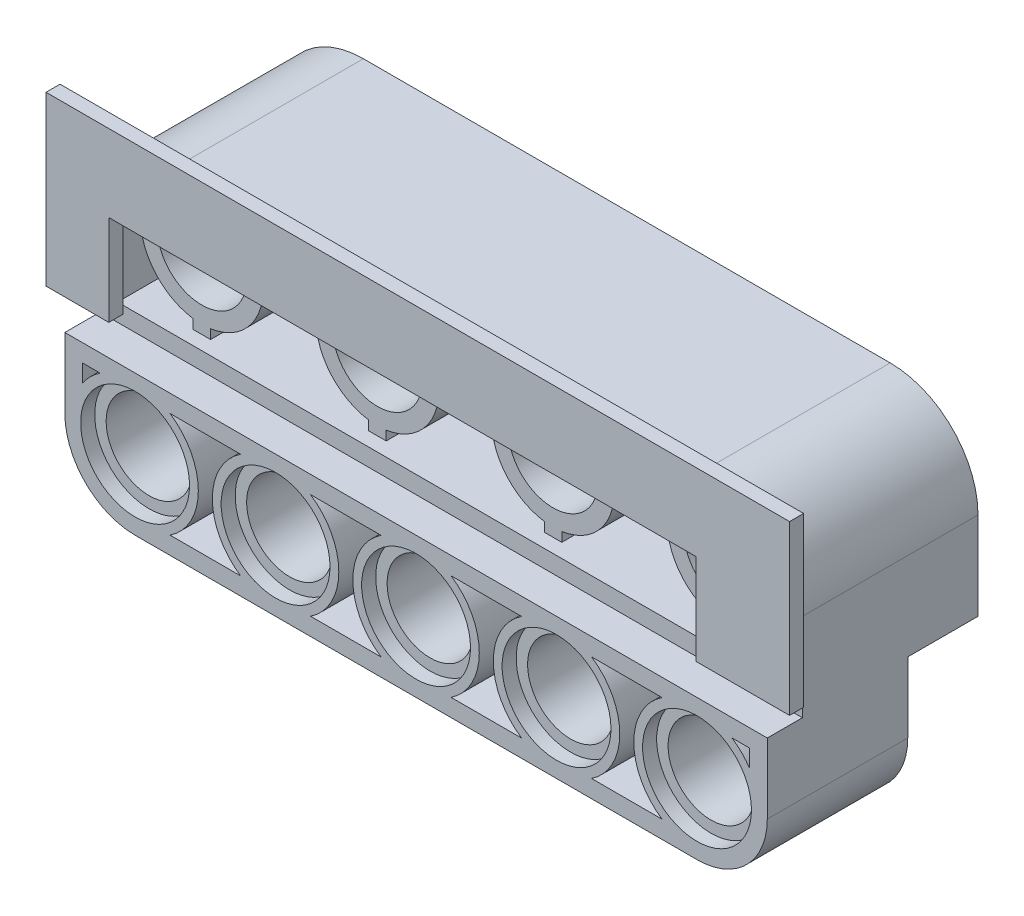
SolidWorks part; units mm, degrees
ref_plane "Front Plane" through (0, 0, 0) normal (0, 0, 1) x (1, 0, 0)
ref_plane "Top Plane" through (0, 0, 0) normal (0, 1, 0) x (1, 0, 0)
ref_plane "Right Plane" through (0, 0, 0) normal (1, 0, 0) x (0, 0, -1)
sketch "Sketch1" plane through (0, 0, 0) normal (1, 0, 0) x (0, 0, -1)
  line L0 (-5, -5) -> (-5, -13)
  line L1 (5, 5) -> (-5, 5)
  line L2 (5, 5) -> (5, -5)
  line L3 (5, -5) -> (-5, -5)
  line L4 (-5, 5) -> (-5, -5)
  line L5 (5, 5) -> (-5, -5) construction
  line L6 (5, -5) -> (-5, 5) construction
  line L7 (-5, -13) -> (3, -13)
  line L8 (3, -13) -> (3, -5)
  point P0 (0, 0)
  dimension "D1" = 10
  dimension "D2" = 10
  dimension "D3" = 8
  dimension "D4" = 8
extrude "Boss-Extrude1" add sketch "Sketch1" along normal blind 40 contours L1 L4 L3 L2 | L7 L8 L3 L0 region at (0, -9, 1) region at (0, 0, 0)
sketch "Sketch2" plane through (0, 0, -5) normal (0, 0, -1) x (-1, 0, 0)
  line L0 (-40, 0) -> (0, 0) construction
  line L1 (-40, 5) -> (-40, -5) construction
  line L2 (0, 5) -> (0, -5) construction
  line L3 (-35, 0) -> (-35, -7.7251) construction
  line L4 (-35, -7.7251) -> (-25, -7.7251) construction
  line L5 (-25, -7.7251) -> (-25, 0) construction
  line L6 (-25, 0) -> (-25, 7.4414) construction
  line L7 (-25, 7.4414) -> (-15, 7.4414) construction
  line L8 (-15, 7.4414) -> (-15, 0) construction
  line L9 (-15, 0) -> (-15, -7.7251) construction
  line L10 (-15, -7.7251) -> (-5, -7.7251) construction
  line L11 (-5, -7.7251) -> (-5, 0) construction
  circle A0 centre (-35, 0) radius 2.5
  circle A1 centre (-25, 0) radius 2.5
  circle A2 centre (-15, 0) radius 2.5
  circle A3 centre (-5, 0) radius 2.5
  dimension "D2" = 5
  dimension "D1" = 5
  dimension "D3" = 10
extrude "Cut-Extrude1" cut sketch "Sketch2" against normal through all
sketch "Sketch3" plane through (0, 0, -3) normal (0, 0, -1) x (-1, 0, 0)
  line L0 (-40, -9) -> (0, -9) construction
  line L1 (-40, -13) -> (-40, -5) construction
  line L2 (0, -13) -> (0, -5) construction
  line L3 (-40, -13) -> (0, -13) construction
  circle A0 centre (-36, -9) radius 2.4
  circle A1 centre (-28, -9) radius 2.4
  circle A2 centre (-20, -9) radius 2.4
  circle A3 centre (-12, -9) radius 2.4
  circle A4 centre (-4, -9) radius 2.4
  circle A5 centre (-36, -9) radius 4 construction
  circle A6 centre (-4, -9) radius 4 construction
  dimension "D1" = 4.8
  dimension "D2" = 8
  dimension "D3" = 8
  dimension "D4" = 8
  dimension "D5" = 8
extrude "Cut-Extrude2" cut sketch "Sketch3" against normal through all
fillet "Fillet1" radius 5 2 edges at (0, 5, 0) (40, 5, 0)
fillet "Fillet2" radius 4 2 edges at (0, -13, 1) (40, -13, 1)
sketch "Sketch4" plane through (0, 0, -3) normal (0, 0, -1) x (-1, 0, 0)
  circle A0 centre (-36, -9) radius 3.1
  circle A1 centre (-28, -9) radius 3.1
  circle A2 centre (-20, -9) radius 3.1
  circle A3 centre (-12, -9) radius 3.1
  circle A4 centre (-4, -9) radius 3.1
  dimension "D1" = 6.2
  dimension "D3" = 8
  dimension "D2" = 5
extrude "Cut-Extrude3" cut sketch "Sketch4" against normal blind 0.8
sketch "Sketch5" plane through (0, 0, 5) normal (0, 0, 1) x (1, 0, 0)
  circle A1 centre (4, -9) radius 3.1
  circle A2 centre (4, -9) radius 3.1
  circle A3 centre (12, -9) radius 3.1
  circle A4 centre (12, -9) radius 3.1
  circle A5 centre (20, -9) radius 3.1
  circle A6 centre (20, -9) radius 3.1
  circle A7 centre (28, -9) radius 3.1
  circle A8 centre (28, -9) radius 3.1
  circle A9 centre (36, -9) radius 3.1
  circle A10 centre (36, -9) radius 3.1
  dimension "D1" = 0
  dimension "D2" = 0
  dimension "D3" = 0
  dimension "D4" = 0
  dimension "D5" = 0
extrude "Cut-Extrude4" cut sketch "Sketch5" against normal blind 0.8
sketch "Sketch6" plane through (0, 0, -5) normal (0, 0, -1) x (-1, 0, 0)
  circle A2 centre (-25, 0) radius 3.5
  circle A3 centre (-35, 0) radius 3.5
  circle A4 centre (-35, 0) radius 3.5
  circle A5 centre (-15, 0) radius 3.5
  circle A6 centre (-5, 0) radius 3.5
  dimension "D1" = 1
  dimension "D3" = 10
  dimension "D2" = 4
extrude "Cut-Extrude5" cut sketch "Sketch6" against normal blind 0.8
sketch "Sketch7" plane through (0, 0, 5) normal (0, 0, 1) x (1, 0, 0)
  circle A1 centre (5, 0) radius 3.5
  circle A2 centre (5, 0) radius 3.5
  circle A3 centre (15, 0) radius 3.5
  circle A4 centre (15, 0) radius 3.5
  circle A5 centre (35, 0) radius 3.5
  circle A6 centre (35, 0) radius 3.5
  circle A7 centre (25, 0) radius 3.5
  circle A8 centre (25, 0) radius 3.5
  dimension "D1" = 0
  dimension "D2" = 0
  dimension "D3" = 0
  dimension "D4" = 0
extrude "Cut-Extrude6" cut sketch "Sketch7" against normal blind 0.8
sketch "Sketch8" plane through (0, 0, -5) normal (0, 0, -1) x (-1, 0, 0)
  line L1 (-5, 4) -> (-35, 4)
  line L2 (-39, 0) -> (-39, -4)
  line L3 (-39, -4) -> (-1, -4)
  line L4 (-1, -4) -> (-1, 0)
  line L5 (0, -5) -> (0, 0)
  line L6 (-5, 5) -> (-35, 5)
  line L7 (-40, 0) -> (-40, -5)
  line L8 (-40, -5) -> (0, -5)
  line L9 (0, -5) -> (0, 0)
  line L10 (-5, 5) -> (-35, 5)
  line L11 (-40, 0) -> (-40, -5)
  line L12 (-40, -5) -> (0, -5)
  arc A0 (-35, 4) -> (-39, 0) centre (-35, 0) ccw
  arc A1 (-1, 0) -> (-5, 4) centre (-5, 0) ccw
  arc A2 (0, 0) -> (-5, 5) centre (-5, 0) ccw
  arc A3 (-35, 5) -> (-40, 0) centre (-35, 0) ccw
  arc A4 (0, 0) -> (-5, 5) centre (-5, 0) ccw
  arc A5 (-35, 5) -> (-40, 0) centre (-35, 0) ccw
  circle A6 centre (-5, 0) radius 3.5 construction
  circle A7 centre (-15, 0) radius 3.5 construction
  circle A8 centre (-25, 0) radius 3.5 construction
  circle A9 centre (-35, 0) radius 3.5 construction
  circle A10 centre (-5, 0) radius 3.5
  circle A11 centre (-15, 0) radius 3.5
  circle A12 centre (-25, 0) radius 3.5
  circle A13 centre (-35, 0) radius 3.5
  circle M13 centre (-5, 0) radius 3.5
  circle M14 centre (-35, 0) radius 3.5
  circle M15 centre (-15, 0) radius 3.5
  circle M16 centre (-25, 0) radius 3.5
  dimension "D1" = 0
  dimension "D2" = 1
extrude "Cut-Extrude7" cut sketch "Sketch8" against normal blind 4.5 contours L4 A1 L1 A0 L2 L3 M13 M15 M16 M14 region at (20, -0.149, -5)
sketch "Sketch9" plane through (0, 0, 5) normal (0, 0, 1) x (1, 0, 0)
  line L4 (0, 0) -> (0, -5)
  line L5 (35, 5) -> (5, 5)
  line L6 (40, -5) -> (40, 0)
  line L7 (0, -5) -> (40, -5)
  line L8 (0, 0) -> (0, -5)
  line L9 (35, 5) -> (5, 5)
  line L10 (40, -5) -> (40, 0)
  line L11 (0, -5) -> (40, -5)
  line L12 (35, 4) -> (5, 4)
  line L13 (39, -4) -> (39, 0)
  line L14 (1, -4) -> (39, -4)
  line L15 (1, 0) -> (1, -4)
  line L16 (35, 4) -> (5, 4)
  line L17 (39, -4) -> (39, 0)
  line L18 (1, -4) -> (39, -4)
  line L19 (1, 0) -> (1, -4)
  circle A1 centre (35, 0) radius 3.5
  arc A2 (5, 5) -> (0, 0) centre (5, 0) ccw
  arc A3 (40, 0) -> (35, 5) centre (35, 0) ccw
  arc A4 (5, 5) -> (0, 0) centre (5, 0) ccw
  arc A5 (40, 0) -> (35, 5) centre (35, 0) ccw
  arc A6 (39, 0) -> (35, 4) centre (35, 0) ccw
  arc A7 (5, 4) -> (1, 0) centre (5, 0) ccw
  arc A8 (39, 0) -> (35, 4) centre (35, 0) ccw
  arc A9 (5, 4) -> (1, 0) centre (5, 0) ccw
  circle A10 centre (35, 0) radius 3.5
  circle A11 centre (25, 0) radius 3.5
  circle A12 centre (25, 0) radius 3.5
  circle A13 centre (15, 0) radius 3.5
  circle A14 centre (15, 0) radius 3.5
  circle A15 centre (5, 0) radius 3.5
  circle A16 centre (5, 0) radius 3.5
  circle M17 centre (5, 0) radius 3.5
  circle M18 centre (25, 0) radius 3.5
  circle M19 centre (35, 0) radius 3.5
  circle M20 centre (15, 0) radius 3.5
  dimension "D1" = 0
  dimension "D2" = 0
  dimension "D3" = 0
  dimension "D4" = 0
  dimension "D5" = 0
  dimension "D6" = 0
extrude "Cut-Extrude8" cut sketch "Sketch9" against normal blind 4.5 contours L16 A9 L19 L18 L17 A8 M18 M20 M19 M17 region at (20, -0.149, 5)
sketch "Sketch10" plane through (0, 0, -3) normal (0, 0, -1) x (-1, 0, 0)
  line L2 (-36, -12) -> (-4, -12)
  line L3 (-36, -12) -> (-4, -12)
  line L4 (-40, -5) -> (0, -5) construction
  line L5 (-39, -9) -> (-39, -5)
  line L6 (-39, -9) -> (-39, -5)
  line L7 (-40, -5) -> (0, -5)
  line L8 (0, -9) -> (0, -5) construction
  line L9 (0, -9) -> (0, -5)
  line L10 (-1, -9) -> (-1, -5)
  line L11 (-40, -6) -> (0, -6)
  circle A0 centre (-36, -9) radius 3.6
  circle A1 centre (-28, -9) radius 3.6
  circle A2 centre (-20, -9) radius 3.6
  circle A3 centre (-12, -9) radius 3.6
  circle A4 centre (-4, -9) radius 3.6
  dimension "D1" = 7.2
  dimension "D5" = 8
  dimension "D6" = 1
  dimension "D2" = 1
  dimension "D3" = 1
  dimension "D7" = 1
  dimension "D4" = 5
extrude "Cut-Extrude9" cut sketch "Sketch10" against normal blind 3.5 contours A1 L11 A0 L3 | A2 L11 A1 L3 | A3 L11 A2 L3 | A4 L11 A3 L3 | A0 L11 L6 | A4 L10 L11 region at (32, -9, -3) region at (38.6862, -6.3138, -3) region at (24, -9, -3) region at (16, -9, -3) region at (1.3138, -6.3138, -3) region at (8, -9, -3)
sketch "Sketch11" plane through (0, 0, 5) normal (0, 0, 1) x (1, 0, 0)
  line L0 (40, -5) -> (0, -5) construction
  line L1 (0, -9) -> (0, -5) construction
  line L2 (39, -9) -> (39, -5) construction
  line L3 (36, -12) -> (4, -12) construction
  line L4 (40, -6) -> (0, -6) construction
  line L5 (1, -9) -> (1, -5) construction
  line L6 (40, -5) -> (0, -5)
  line L7 (0, -9) -> (0, -5)
  line L8 (39, -9) -> (39, -5)
  line L9 (36, -12) -> (4, -12)
  line L10 (40, -6) -> (0, -6)
  line L11 (1, -9) -> (1, -5)
  circle A1 centre (12, -9) radius 3.6
  circle A2 centre (12, -9) radius 3.6
  circle A3 centre (20, -9) radius 3.6
  circle A4 centre (20, -9) radius 3.6
  circle A5 centre (28, -9) radius 3.6
  circle A6 centre (28, -9) radius 3.6
  circle A7 centre (36, -9) radius 3.6
  circle A8 centre (36, -9) radius 3.6
  circle A9 centre (4, -9) radius 3.6
  circle A10 centre (4, -9) radius 3.6
  dimension "D1" = 0
  dimension "D2" = 0
  dimension "D3" = 0
  dimension "D4" = 0
  dimension "D5" = 0
extrude "Cut-Extrude10" cut sketch "Sketch11" against normal blind 3.5 contours A10 L9 A2 L10 | A4 L10 A2 L9 | A6 L10 A4 L9 | A8 L10 A6 L9 | A8 L8 L10 | A10 L10 L11 region at (38.6862, -6.3138, 5) region at (1.3138, -6.3138, 5) region at (32, -9, 5) region at (8, -9, 5) region at (24, -9, 5) region at (16, -9, 5)
sketch "Sketch12" plane through (0, 0, -4.2) normal (0, 0, -1) x (-1, 0, 0)
  line L1 (-39, 0) -> (2.7351, 0) construction
  line L2 (-39, -0.5) -> (2.7351, -0.5)
  line L3 (-39, 0.5) -> (2.7351, 0.5)
  line L4 (-35, 4) -> (-35, -4) construction
  line L5 (-1, -4) -> (-1, 0)
  line L6 (-39, -4) -> (-1, -4)
  line L7 (-39, 0) -> (-39, -4)
  line L8 (-5, 4) -> (-35, 4)
  line L9 (-1, -4) -> (-1, 0)
  line L10 (-39, -4) -> (-1, -4)
  line L11 (-39, 0) -> (-39, -4)
  line L12 (-5, 4) -> (-35, 4)
  line L13 (-35.5, 4) -> (-35.5, -4)
  line L14 (-34.5, 4) -> (-34.5, -4)
  line L15 (-24.5, 4) -> (-24.5, -4)
  line L16 (-25.5, 4) -> (-25.5, -4)
  line L17 (-14.5, 4) -> (-14.5, -4)
  line L18 (-15.5, 4) -> (-15.5, -4)
  line L19 (-4.5, 4) -> (-4.5, -4)
  line L20 (-5.5, 4) -> (-5.5, -4)
  circle A0 centre (-5, 0) radius 3.5 construction
  circle A1 centre (-15, 0) radius 3.5 construction
  circle A2 centre (-25, 0) radius 3.5 construction
  circle A3 centre (-35, 0) radius 3.5 construction
  circle A4 centre (-5, 0) radius 3.5
  circle A5 centre (-15, 0) radius 3.5
  circle A6 centre (-25, 0) radius 3.5
  circle A7 centre (-35, 0) radius 3.5
  arc A10 (-35, 4) -> (-39, 0) centre (-35, 0) ccw
  arc A11 (-1, 0) -> (-5, 4) centre (-5, 0) ccw
  arc A12 (-35, 4) -> (-39, 0) centre (-35, 0) ccw
  arc A13 (-1, 0) -> (-5, 4) centre (-5, 0) ccw
  circle M14 centre (-35, 0) radius 3.5
  dimension "D7" = 10
  dimension "D1" = 0
  dimension "D2" = 0.5
  dimension "D3" = 0.5
  dimension "D4" = 0.5
  dimension "D5" = 0.5
  dimension "D6" = 4
extrude "Boss-Extrude2" add sketch "Sketch12" against normal up to surface (3.7 mm away) contours A6 L3 L2 M14 | A6 L2 A5 L3 | A6 L15 L12 L16 | L12 A12 L13 L14 M14 | L3 A12 L11 L2 M14 | A6 L16 L10 L15 | L14 L13 L10 M14 | A5 L18 L10 L17 | A5 L17 L12 L18 | A5 L2 A4 L3 | L19 A13 L12 L20 A4 | A4 L20 L10 L19 | L9 A13 L3 A4 L2 region at (38.7414, -0.0039, -4.2) region at (35, -3.7439, -4.2) region at (34.9961, 3.7414, -4.2) region at (30, 0, -4.2) region at (25, -3.7439, -4.2) region at (25, 3.7439, -4.2) region at (15, -3.7439, -4.2) region at (20, 0, -4.2) region at (15, 3.7439, -4.2) region at (5, -3.7439, -4.2) region at (10, 0, -4.2) region at (5.0039, 3.7414, -4.2) region at (1.2586, -0.0039, -4.2) up to face at (5, 3.5, -0.5)
sketch "Sketch13" plane through (0, 0, 4.2) normal (0, 0, 1) x (1, 0, 0)
  line L0 (39, -0.5) -> (-2.7351, -0.5) construction
  line L1 (25.5, 4) -> (25.5, -4) construction
  line L2 (34.5, 4) -> (34.5, -4) construction
  line L3 (35.5, 4) -> (35.5, -4) construction
  line L4 (39, -4) -> (39, 0)
  line L5 (35, 4) -> (5, 4)
  line L6 (1, 0) -> (1, -4)
  line L7 (1, -4) -> (39, -4)
  line L8 (39, -4) -> (39, 0)
  line L9 (35, 4) -> (5, 4)
  line L10 (1, 0) -> (1, -4)
  line L11 (1, -4) -> (39, -4)
  line L12 (39, 0.5) -> (-2.7351, 0.5) construction
  line L13 (5.5, 4) -> (5.5, -4) construction
  line L14 (4.5, 4) -> (4.5, -4) construction
  line L15 (15.5, 4) -> (15.5, -4) construction
  line L16 (14.5, 4) -> (14.5, -4) construction
  line L17 (24.5, 4) -> (24.5, -4) construction
  line L18 (39, -0.5) -> (-2.7351, -0.5)
  line L19 (25.5, 4) -> (25.5, -4)
  line L20 (34.5, 4) -> (34.5, -4)
  line L21 (35.5, 4) -> (35.5, -4)
  line L22 (39, 0.5) -> (-2.7351, 0.5)
  line L23 (5.5, 4) -> (5.5, -4)
  line L24 (4.5, 4) -> (4.5, -4)
  line L25 (15.5, 4) -> (15.5, -4)
  line L26 (14.5, 4) -> (14.5, -4)
  line L27 (24.5, 4) -> (24.5, -4)
  circle A1 centre (35, 0) radius 3.5
  circle A2 centre (35, 0) radius 3.5
  circle A3 centre (25, 0) radius 3.5
  circle A4 centre (25, 0) radius 3.5
  circle A5 centre (15, 0) radius 3.5
  circle A6 centre (15, 0) radius 3.5
  circle A7 centre (5, 0) radius 3.5
  circle A8 centre (5, 0) radius 3.5
  arc A10 (39, 0) -> (35, 4) centre (35, 0) ccw
  arc A11 (5, 4) -> (1, 0) centre (5, 0) ccw
  arc A12 (39, 0) -> (35, 4) centre (35, 0) ccw
  arc A13 (5, 4) -> (1, 0) centre (5, 0) ccw
  circle M11 centre (15, 0) radius 3.5
  dimension "D1" = 0
  dimension "D2" = 0
  dimension "D3" = 0
  dimension "D4" = 0
  dimension "D5" = 0
extrude "Boss-Extrude3" add sketch "Sketch13" against normal up to surface (3.7 mm away) contours L9 L26 L25 M11 | L9 A13 L24 A8 L23 | L22 A13 L10 L18 A8 | A8 L24 L11 L23 | A8 L18 L22 M11 | L26 L11 L25 M11 | A4 L22 L18 M11 | A4 L19 L9 L27 | A4 L18 A2 L22 | A4 L27 L11 L19 | L21 A12 L9 L20 A2 | L8 A12 L22 A2 L18 | A2 L20 L11 L21 region at (38.7414, -0.0039, 4.2) region at (35, -3.7439, 4.2) region at (25, -3.7439, 4.2) region at (34.9961, 3.7414, 4.2) region at (30, 0, 4.2) region at (15, -3.7439, 4.2) region at (20, 0, 4.2) region at (25, 3.7439, 4.2) region at (5, -3.7439, 4.2) region at (10, 0, 4.2) region at (15, 3.7439, 4.2) region at (1.2586, -0.0039, 4.2) region at (5.0039, 3.7414, 4.2) up to face at (28.5, 0, 0.5)
sketch "Sketch14" plane through (0, 0, -3) normal (0, 0, -1) x (-1, 0, 0)
  line L1 (-39, -6) -> (-39, -5)
  line L2 (-40, -5) -> (0, -5) construction
  line L3 (-39, -6) -> (-37.99, -6)
  line L4 (-37.99, -6) -> (-37.99, -5)
  line L5 (-37.99, -5) -> (-39, -5)
  line L6 (-34.01, -6) -> (-34.01, -5)
  line L7 (-40, -5) -> (0, -5) construction
  line L8 (-34.01, -6) -> (-29.99, -6)
  line L9 (-29.99, -6) -> (-29.99, -5)
  line L10 (-29.99, -5) -> (-34.01, -5)
  line L11 (-26.01, -6) -> (-26.01, -5)
  line L12 (-26.01, -6) -> (-21.99, -6)
  line L13 (-21.99, -6) -> (-21.99, -5)
  line L14 (-21.99, -5) -> (-26.01, -5)
  line L15 (-18.01, -6) -> (-18.01, -5)
  line L16 (-18.01, -6) -> (-13.99, -6)
  line L17 (-13.99, -6) -> (-13.99, -5)
  line L18 (-13.99, -5) -> (-18.01, -5)
  line L19 (-10.01, -6) -> (-10.01, -5)
  line L20 (-10.01, -6) -> (-5.99, -6)
  line L21 (-5.99, -6) -> (-5.99, -5)
  line L22 (-5.99, -5) -> (-10.01, -5)
  line L23 (-1, -6) -> (-2.01, -6)
  line L24 (-2.01, -6) -> (-2.01, -5)
  line L25 (-2.01, -5) -> (-1, -5)
  line L26 (-1, -5) -> (-1, -6)
  dimension "D1" = 4
  dimension "D2" = 8
extrude "Cut-Extrude11" [suppressed] cut sketch "Sketch14" against normal up to surface (3.5 mm away) up to face at (24, -9, 0.5)
sketch "Sketch15" plane through (0, 0, 5) normal (0, 0, 1) x (1, 0, 0)
  line L4 (34.01, -6) -> (34.01, -5)
  line L5 (34.01, -5) -> (29.99, -5)
  line L6 (29.99, -5) -> (29.99, -6)
  line L7 (29.99, -6) -> (34.01, -6)
  line L8 (34.01, -6) -> (34.01, -5)
  line L9 (34.01, -5) -> (29.99, -5)
  line L10 (29.99, -5) -> (29.99, -6)
  line L11 (29.99, -6) -> (34.01, -6)
  line L12 (39, -6) -> (39, -5)
  line L13 (39, -5) -> (37.99, -5)
  line L14 (37.99, -5) -> (37.99, -6)
  line L15 (37.99, -6) -> (39, -6)
  line L16 (39, -6) -> (39, -5)
  line L17 (39, -5) -> (37.99, -5)
  line L18 (37.99, -5) -> (37.99, -6)
  line L19 (37.99, -6) -> (39, -6)
  line L20 (10.01, -6) -> (10.01, -5)
  line L21 (10.01, -5) -> (5.99, -5)
  line L22 (5.99, -5) -> (5.99, -6)
  line L23 (5.99, -6) -> (10.01, -6)
  line L24 (10.01, -6) -> (10.01, -5)
  line L25 (10.01, -5) -> (5.99, -5)
  line L26 (5.99, -5) -> (5.99, -6)
  line L27 (5.99, -6) -> (10.01, -6)
  line L28 (18.01, -6) -> (18.01, -5)
  line L29 (18.01, -5) -> (13.99, -5)
  line L30 (13.99, -5) -> (13.99, -6)
  line L31 (13.99, -6) -> (18.01, -6)
  line L32 (18.01, -6) -> (18.01, -5)
  line L33 (18.01, -5) -> (13.99, -5)
  line L34 (13.99, -5) -> (13.99, -6)
  line L35 (13.99, -6) -> (18.01, -6)
  line L36 (26.01, -6) -> (26.01, -5)
  line L37 (26.01, -5) -> (21.99, -5)
  line L38 (21.99, -5) -> (21.99, -6)
  line L39 (21.99, -6) -> (26.01, -6)
  line L40 (26.01, -6) -> (26.01, -5)
  line L41 (26.01, -5) -> (21.99, -5)
  line L42 (21.99, -5) -> (21.99, -6)
  line L43 (21.99, -6) -> (26.01, -6)
  line L44 (2.01, -5) -> (1, -5)
  line L45 (1, -5) -> (1, -6)
  line L46 (1, -6) -> (2.01, -6)
  line L47 (2.01, -6) -> (2.01, -5)
  line L48 (2.01, -5) -> (1, -5)
  line L49 (1, -5) -> (1, -6)
  line L50 (1, -6) -> (2.01, -6)
  line L51 (2.01, -6) -> (2.01, -5)
  dimension "D1" = 0
  dimension "D2" = 0
  dimension "D3" = 0
  dimension "D4" = 0
  dimension "D5" = 0
  dimension "D6" = 0
extrude "Cut-Extrude12" [suppressed] cut sketch "Sketch15" against normal up to surface (3.5 mm away) up to face at (24, -9, 1.5)
ref_plane "Plane1" through (0, -5, 0) normal (0, -1, 0) x (-1, 0, 0)
split "Split1" trim tools "Plane1" bodies to split 113 resulting bodies 116 117
move or copy body "Body-Move/Copy1" bodies to move or copy 117 copy no translate (0, 0, -2)
combine bodies "Combine1" operation type add bodies to combine 116 118
sketch "Sketch16" plane through (0, 0, -6.2) normal (0, 0, -1) x (-1, 0, 0)
  circle A0 centre (-35, 0) radius 2.55
  circle A1 centre (-25, 0) radius 2.55
  circle A2 centre (-15, 0) radius 2.55
  circle A3 centre (-5, 0) radius 2.55
  circle A4 centre (-36, -9) radius 2.45
  circle A5 centre (-28, -9) radius 2.45
  circle A6 centre (-20, -9) radius 2.45
  circle A7 centre (-12, -9) radius 2.45
  circle A8 centre (-4, -9) radius 2.45
  dimension "D1" = 4.9
  dimension "D2" = 5.1
extrude "Cut-Extrude13" cut sketch "Sketch16" against normal through all and the other way through all
sketch "Sketch17" plane through (0, 0, 3) normal (0, 0, 1) x (1, 0, 0)
  circle A0 centre (1.8894, 3.2518) radius 0.5
  circle A1 centre (9.7939, 4.5) radius 0.5
  circle A2 centre (0.5, -2.267) radius 0.5
  circle A3 centre (19.8442, 4.5) radius 0.5
  circle A4 centre (29.8945, 4.5) radius 0.5
  circle A5 centre (37.8277, 3.5006) radius 0.5
  circle A6 centre (39.5, -2.0904) radius 0.5
  point P0 (9.7939, 4.5)
extrude "Boss-Extrude4" add sketch "Sketch17" along normal up to surface (2 mm away) up to face at (20, 0.2761, 3)
sketch "Sketch18" plane through (0, 0, 5) normal (0, 0, 1) x (1, 0, 0)
  line L1 (-1.0736, 6.3091) -> (41.2687, 6.3091)
  line L2 (-1.0736, 6.3091) -> (-1.0736, -3.252)
  line L3 (-1.0736, -3.252) -> (41.2687, -3.252)
  line L4 (41.2687, 6.3091) -> (41.2687, -3.252)
  line L5 (2.5037, -3.252) -> (35.9352, -3.252)
  line L6 (2.5037, -3.252) -> (2.5037, 1.9188)
  line L7 (2.5037, 1.9188) -> (35.9352, 1.9188)
  line L8 (35.9352, -3.252) -> (35.9352, 1.9188)
  circle M1 centre (0.5, -2.267) radius 0.5
extrude "Boss-Extrude5" add sketch "Sketch18" against normal blind 0.8 contours L8 L3 L4 L1 L2 L6 L7 M1 region at (20.8207, 3.1829, 5)
